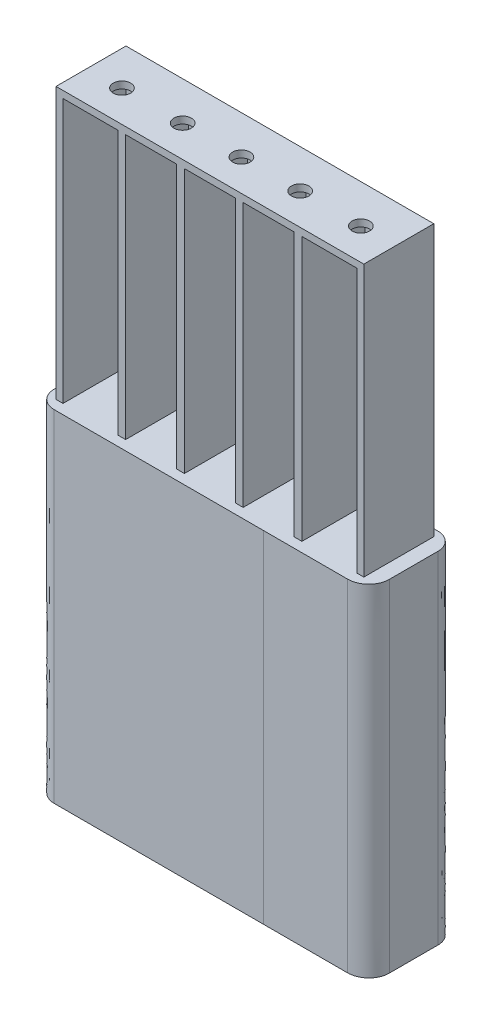
SolidWorks part; units mm, degrees
ref_plane "Front Plane" through (0, 0, 0) normal (0, 0, 1) x (1, 0, 0)
ref_plane "Top Plane" through (0, 0, 0) normal (0, 1, 0) x (1, 0, 0)
ref_plane "Right Plane" through (0, 0, 0) normal (1, 0, 0) x (0, 0, -1)
ref_plane "Plane1" through (0, 10, 0) normal (0, 1, 0) x (1, 0, 0)
sketch "Sketch1" plane through (0, 0, 0) normal (0, 0, 1) x (1, 0, 0)
  line L1 (-44, -87.5) -> (44, -87.5)
  line L2 (-44, -87.5) -> (-44, 87.5)
  line L3 (-44, 87.5) -> (44, 87.5)
  line L4 (44, -87.5) -> (44, 87.5)
  line L5 (-44, -87.5) -> (44, 87.5) construction
  line L6 (-44, 87.5) -> (44, -87.5) construction
  point P0 (0, 0)
  dimension "D1" = 88
  dimension "D2" = 175
extrude "Boss-Extrude1" add sketch "Sketch1" along normal blind 2
sketch "Sketch2" plane through (0, 0, 2) normal (0, 0, 1) x (1, 0, 0)
  line L4 (44, -87.5) -> (44, 87.5)
  line L5 (44, 87.5) -> (-44, 87.5)
  line L6 (-44, 87.5) -> (-44, -87.5)
  line L7 (-44, -87.5) -> (44, -87.5)
  line L8 (44, -87.5) -> (44, 87.5)
  line L9 (44, 87.5) -> (-44, 87.5)
  line L10 (-44, 87.5) -> (-44, -87.5)
  line L11 (-44, -87.5) -> (44, -87.5)
  dimension "D1" = 0
extrude "Extrude-Thin1" add sketch "Sketch2" along normal blind 18 thin thin type one direction reverse wall 2
sketch "Sketch3" plane through (0, 0, 2) normal (0, 0, 1) x (1, 0, 0)
  line L0 (-25.2, 85.5) -> (-25.2, -85.5)
  line L1 (42, 85.5) -> (-42, 85.5) construction
  line L2 (-42, -85.5) -> (42, -85.5) construction
  line L3 (-8.4, 85.5) -> (-8.4, -85.5)
  line L4 (42, 85.5) -> (-42, 85.5) construction
  line L5 (25.2, 85.5) -> (25.2, -85.5)
  line L6 (8.4, 85.5) -> (8.4, -85.5)
  line L7 (-42, -85.5) -> (42, -85.5) construction
  line L8 (-42, 85.5) -> (-42, -85.5) construction
  line L9 (42, -85.5) -> (42, 85.5) construction
  dimension "D1" = 16.8
  dimension "D2" = 16.8
  dimension "D3" = 16.8
  dimension "D4" = 16.8
  dimension "D5" = 16.8
extrude "Extrude-Thin2" add sketch "Sketch3" along normal blind 18 thin thin type mid plane wall 2.2
sketch "Sketch4" plane through (0, 87.5, 0) normal (0, 1, 0) x (1, 0, 0)
  line L0 (26.3, -20) -> (26.3, -2) construction
  line L1 (26.3, -2) -> (42, -2) construction
  line L2 (42, -2) -> (42, -20) construction
  line L3 (42, -20) -> (26.3, -20) construction
  line L4 (9.5, -20) -> (9.5, -2) construction
  line L5 (9.5, -2) -> (24.1, -2) construction
  line L6 (24.1, -2) -> (24.1, -20) construction
  line L7 (24.1, -20) -> (9.5, -20) construction
  line L8 (-7.3, -2) -> (7.3, -2) construction
  line L9 (7.3, -2) -> (7.3, -20) construction
  line L10 (7.3, -20) -> (-7.3, -20) construction
  line L11 (-7.3, -20) -> (-7.3, -2) construction
  line L12 (-24.1, -2) -> (-9.5, -2) construction
  line L13 (-9.5, -2) -> (-9.5, -20) construction
  line L14 (-9.5, -20) -> (-24.1, -20) construction
  line L15 (-24.1, -20) -> (-24.1, -2) construction
  line L16 (-42, -2) -> (-26.3, -2) construction
  line L17 (-26.3, -2) -> (-26.3, -20) construction
  line L18 (-26.3, -20) -> (-42, -20) construction
  line L19 (-42, -20) -> (-42, -2) construction
  line L20 (26.3, -20) -> (26.3, -2) construction
  line L21 (26.3, -2) -> (42, -2) construction
  line L22 (42, -2) -> (42, -20) construction
  line L23 (42, -20) -> (26.3, -20) construction
  line L24 (9.5, -20) -> (9.5, -2) construction
  line L25 (9.5, -2) -> (24.1, -2) construction
  line L26 (24.1, -2) -> (24.1, -20) construction
  line L27 (24.1, -20) -> (9.5, -20) construction
  line L28 (-7.3, -2) -> (7.3, -2) construction
  line L29 (7.3, -2) -> (7.3, -20) construction
  line L30 (7.3, -20) -> (-7.3, -20) construction
  line L31 (-7.3, -20) -> (-7.3, -2) construction
  line L32 (-24.1, -2) -> (-9.5, -2) construction
  line L33 (-9.5, -2) -> (-9.5, -20) construction
  line L34 (-9.5, -20) -> (-24.1, -20) construction
  line L35 (-24.1, -20) -> (-24.1, -2) construction
  line L36 (-42, -2) -> (-26.3, -2) construction
  line L37 (-26.3, -2) -> (-26.3, -20) construction
  line L38 (-26.3, -20) -> (-42, -20) construction
  line L39 (-42, -20) -> (-42, -2) construction
  line L40 (42, -11) -> (-42, -11) construction
  line L41 (-16.8, -20) -> (-16.8, -2) construction
  line L42 (-34.15, -20) -> (-34.15, -2) construction
  line L43 (0, -20) -> (0, -2) construction
  line L44 (16.8, -20) -> (16.8, -2) construction
  line L45 (34.15, -20) -> (34.15, -2) construction
  point P26 (34.15, -11)
  point P28 (16.8, -11)
  point P30 (0, -11)
  point P31 (-16.8, -11)
  point P34 (-34.15, -11)
hole_wizard "Ø5.0mm Dowel Hole3" positions "Sketch5" profile "Sketch6" hole size "Ø5.0" standard "BSI" end condition up to next
sketch "Sketch5" plane through (0, 87.5, 0) normal (0, 1, 0) x (1, 0, 0)
  line L0 (-34.15, -20) -> (-34.15, -2) construction
  line L1 (-16.8, -20) -> (-16.8, -2) construction
  point P0 (-34.15, -11)
  point P4 (-16.8, -11)
  point P8 (0, -11)
  point P11 (16.8, -11)
  point P14 (34.15, -11)
sketch "Sketch6" plane through (-34.15, 87.5, 11) normal (1, 0, 0) x (0, 0, 1)
  line L0 (0, 0) -> (0, 2)
  line L1 (0, 2) -> (2.5, 2)
  line L2 (2.5, 2) -> (2.5, 0)
  line L5 (2.5, 0) -> (0, 0)
  line L11 (0, -6.35) -> (0, 107.95) construction
  dimension "Thru Hole Dia." = 5
  dimension "Thru Hole Depth" = 2
sketch "Sketch7" plane through (0, 10, 0) normal (0, -1, 0) x (1, 0, 0)
  line L5 (-41.7947, -2) -> (43.1333, -2)
  line L6 (48.2045, 2.9357) -> (48.2045, 16.9113)
  line L7 (42.125, 22.8183) -> (18.1019, 22.8081)
  line L8 (18.1019, 22.8081) -> (-41.7556, 22.7981)
  line L9 (-46.7955, 17.7993) -> (-46.7955, 2.97)
  line L10 (-41.7947, -2) -> (43.1333, -2)
  line L11 (48.2045, 2.9357) -> (48.2045, 16.9113)
  line L12 (42.125, 22.8183) -> (18.1019, 22.8081)
  line L13 (18.1019, 22.8081) -> (-41.7556, 22.7981)
  line L14 (-46.7955, 17.7993) -> (-46.7955, 2.97)
  spline S4 degree 3 poles (-2663.4049, 14747.336) (-351.3772, 1466.2285) (-27.6531, -15.4623) (44.4297, -1.8483) (44.748, -1.7568) (45.359, -1.5153) (45.6493, -1.3671) (46.1994, -1.0159) (46.4616, -0.8102) (46.9336, -0.3574) (47.1455, -0.1099) (47.4262, 0.2936) (47.514, 0.4343) (47.6737, 0.7219) (47.7457, 0.8688) (47.9389, 1.3182) (48.0374, 1.6296) (63.8602, 78.2771) (-1778.904, 382.2974) (-4916.21, -13939.9034) knots -27.879644 -27.879644 -27.879644 -27.879644 0.125 0.125 0.25 0.25 0.375 0.375 0.5 0.5 0.625 0.625 0.6875 0.6875 0.75 0.75 0.875 0.875 30.345228 30.345228 30.345228 30.345228 only from (43.1333, -2) to (48.2045, 2.9357)
  spline S5 degree 3 poles (-14693.5212, -2728.0041) (-1558.4787, -417.9441) (64.2048, -60.9232) (48.0477, 18.2712) (47.9989, 18.461) (47.8815, 18.8372) (47.8126, 19.0236) (47.5808, 19.5649) (47.3916, 19.9066) (47.0561, 20.3904) (46.9348, 20.5478) (46.6788, 20.8475) (46.5441, 20.9899) (46.1207, 21.3956) (45.8129, 21.6376) (45.1451, 22.0633) (44.7957, 22.2403) (44.0682, 22.5266) (43.6865, 22.6364) (-95.6501, 48.8334) (-800.4618, -4615.6594) (-2172.0781, -14807.512) knots -25.66642 -25.66642 -25.66642 -25.66642 0.125 0.125 0.1875 0.1875 0.25 0.25 0.375 0.375 0.4375 0.4375 0.5 0.5 0.625 0.625 0.75 0.75 0.875 0.875 45.745203 45.745203 45.745203 45.745203 only from (48.2045, 16.9113) to (42.125, 22.8183)
  spline S6 degree 3 poles (2667.3323, -14725.6736) (306.981, -1238.0017) (22.7913, 35.5557) (-42.894, 22.6717) (-43.053, 22.6324) (-43.3684, 22.5381) (-43.5253, 22.4827) (-43.982, 22.2959) (-44.271, 22.1434) (-44.8182, 21.7829) (-45.0779, 21.5726) (-45.5439, 21.1126) (-45.7531, 20.8616) (-46.0304, 20.4526) (-46.1168, 20.3104) (-46.2734, 20.0213) (-46.3441, 19.8738) (-46.534, 19.422) (-46.6314, 19.1076) (-67.1587, -82.3417) (3093.0366, -526.8499) (14825.7993, -1896.8517) knots -25.413819 -25.413819 -25.413819 -25.413819 0.125 0.125 0.1875 0.1875 0.25 0.25 0.375 0.375 0.5 0.5 0.625 0.625 0.6875 0.6875 0.75 0.75 0.875 0.875 39.8413 39.8413 39.8413 39.8413 only from (-41.7556, 22.7981) to (-46.7955, 17.7993)
  spline S7 degree 3 poles (14701.294, 2714.3452) (1271.9799, 363.0065) (-59.8955, 68.1746) (-46.6679, 1.8393) (-46.6283, 1.6814) (-46.5331, 1.3683) (-46.4771, 1.2127) (-46.2887, 0.7605) (-46.1349, 0.4746) (-45.7714, -0.0662) (-45.5599, -0.3219) (-45.0982, -0.7797) (-44.8463, -0.985) (-44.2993, -1.3471) (-44.009, -1.5004) (-43.4082, -1.7468) (-43.0937, -1.8415) (64.0613, -22.9318) (564.7803, 3436.7994) (1966.4877, 14858.5351) knots -25.848129 -25.848129 -25.848129 -25.848129 0.125 0.125 0.1875 0.1875 0.25 0.25 0.375 0.375 0.5 0.5 0.625 0.625 0.75 0.75 0.875 0.875 42.339834 42.339834 42.339834 42.339834 only from (-46.7955, 2.97) to (-41.7947, -2)
  spline S8 degree 3 poles (43.1333, -2) (43.4638, -2) (43.7891, -1.9693) (44.4297, -1.8483) (44.748, -1.7568) (45.359, -1.5153) (45.6493, -1.3671) (46.1994, -1.0159) (46.4616, -0.8102) (46.9336, -0.3574) (47.1455, -0.1099) (47.4262, 0.2936) (47.514, 0.4343) (47.6737, 0.7219) (47.7457, 0.8688) (47.9389, 1.3182) (48.0374, 1.6296) (48.1711, 2.2771) (48.2045, 2.6049) (48.2045, 2.9357) knots 0 0 0 0 0.125 0.125 0.25 0.25 0.375 0.375 0.5 0.5 0.625 0.625 0.6875 0.6875 0.75 0.75 0.875 0.875 1 1 1 1
  spline S9 degree 3 poles (48.2045, 16.9113) (48.2045, 17.3074) (48.1648, 17.6968) (48.0477, 18.2712) (47.9989, 18.461) (47.8815, 18.8372) (47.8126, 19.0236) (47.5808, 19.5649) (47.3916, 19.9066) (47.0561, 20.3904) (46.9348, 20.5478) (46.6788, 20.8475) (46.5441, 20.9899) (46.1207, 21.3956) (45.8129, 21.6376) (45.1451, 22.0633) (44.7957, 22.2403) (44.0682, 22.5266) (43.6865, 22.6364) (42.9123, 22.7819) (42.5209, 22.8183) (42.125, 22.8183) knots 0 0 0 0 0.125 0.125 0.1875 0.1875 0.25 0.25 0.375 0.375 0.4375 0.4375 0.5 0.5 0.625 0.625 0.75 0.75 0.875 0.875 1 1 1 1
  spline S10 degree 3 poles (-41.7556, 22.7981) (-42.087, 22.7981) (-42.4129, 22.766) (-42.894, 22.6717) (-43.053, 22.6324) (-43.3684, 22.5381) (-43.5253, 22.4827) (-43.982, 22.2959) (-44.271, 22.1434) (-44.8182, 21.7829) (-45.0779, 21.5726) (-45.5439, 21.1126) (-45.7531, 20.8616) (-46.0304, 20.4526) (-46.1168, 20.3104) (-46.2734, 20.0213) (-46.3441, 19.8738) (-46.534, 19.422) (-46.6314, 19.1076) (-46.7626, 18.4588) (-46.7955, 18.1308) (-46.7955, 17.7993) knots 0 0 0 0 0.125 0.125 0.1875 0.1875 0.25 0.25 0.375 0.375 0.5 0.5 0.625 0.625 0.6875 0.6875 0.75 0.75 0.875 0.875 1 1 1 1
  spline S11 degree 3 poles (-46.7955, 2.97) (-46.7955, 2.6408) (-46.7632, 2.317) (-46.6679, 1.8393) (-46.6283, 1.6814) (-46.5331, 1.3683) (-46.4771, 1.2127) (-46.2887, 0.7605) (-46.1349, 0.4746) (-45.7714, -0.0662) (-45.5599, -0.3219) (-45.0982, -0.7797) (-44.8463, -0.985) (-44.2993, -1.3471) (-44.009, -1.5004) (-43.4082, -1.7468) (-43.0937, -1.8415) (-42.4496, -1.9682) (-42.1239, -2) (-41.7947, -2) knots 0 0 0 0 0.125 0.125 0.1875 0.1875 0.25 0.25 0.375 0.375 0.5 0.5 0.625 0.625 0.75 0.75 0.875 0.875 1 1 1 1
  dimension "D1" = 0
extrude "Boss-Extrude2" add sketch "Sketch7" along normal up to surface (97.5 mm away) up to face at (0, -87.5, 10)
